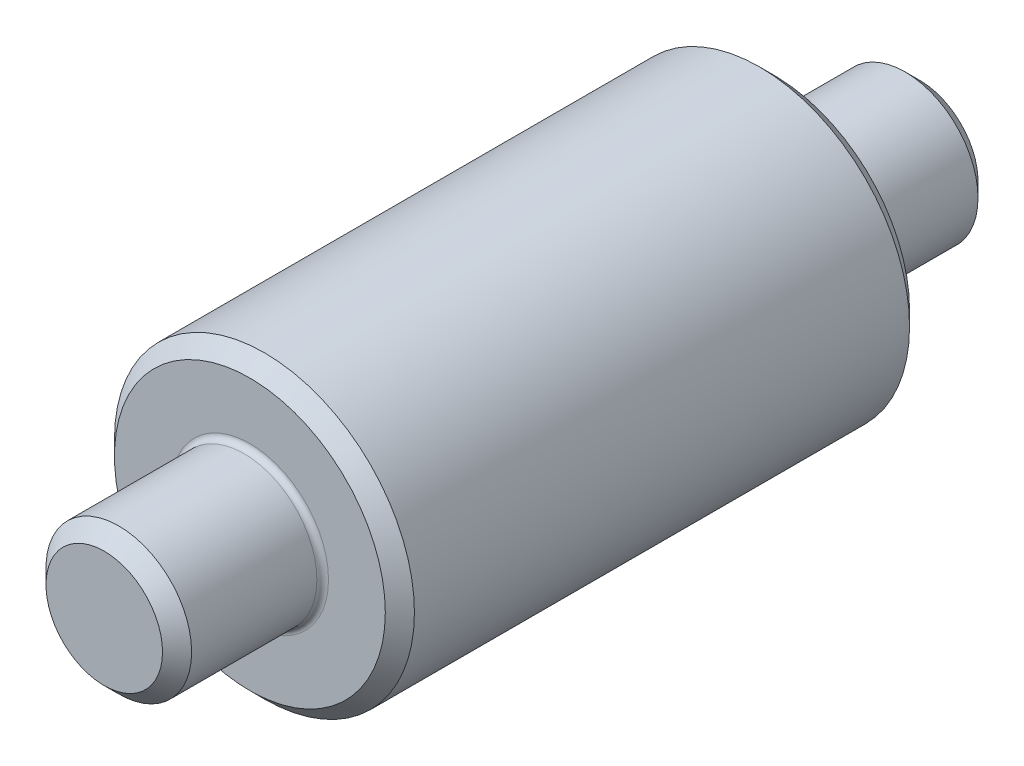
SolidWorks part; units mm, degrees
ref_plane "정면" through (0, 0, 0) normal (0, 0, 1) x (1, 0, 0)
ref_plane "윗면" through (0, 0, 0) normal (0, 1, 0) x (1, 0, 0)
ref_plane "우측면" through (0, 0, 0) normal (1, 0, 0) x (0, 0, -1)
sketch "Sketch1" plane through (0, 0, 0) normal (0, 0, 1) x (1, 0, 0)
  circle A0 centre (0, 0) radius 5.15
  dimension "D1" = 10.3
extrude "Boss-Extrude1" add sketch "Sketch1" along normal blind 9 and the other way blind 9
sketch "Sketch2" plane through (0, 0, 9) normal (0, 0, 1) x (1, 0, 0)
  circle A0 centre (0, 0) radius 2.5
  dimension "D1" = 5
extrude "Boss-Extrude2" add sketch "Sketch2" along normal blind 5
sketch "Sketch3" plane through (0, 0, -9) normal (0, 0, -1) x (-1, 0, 0)
  circle A0 centre (0, 0) radius 2.5
  dimension "D1" = 5
extrude "Boss-Extrude3" add sketch "Sketch3" along normal blind 5
chamfer "Chamfer2" distance 0.5 angle 45 4 edges at (-2.5, 0, -14) (2.5, 0, 14) (5.15, 0, -9) (5.15, 0, 9)
fillet "Fillet1" radius 0.2 2 edges at (-2.5, 0, -9) (2.5, 0, 9)
